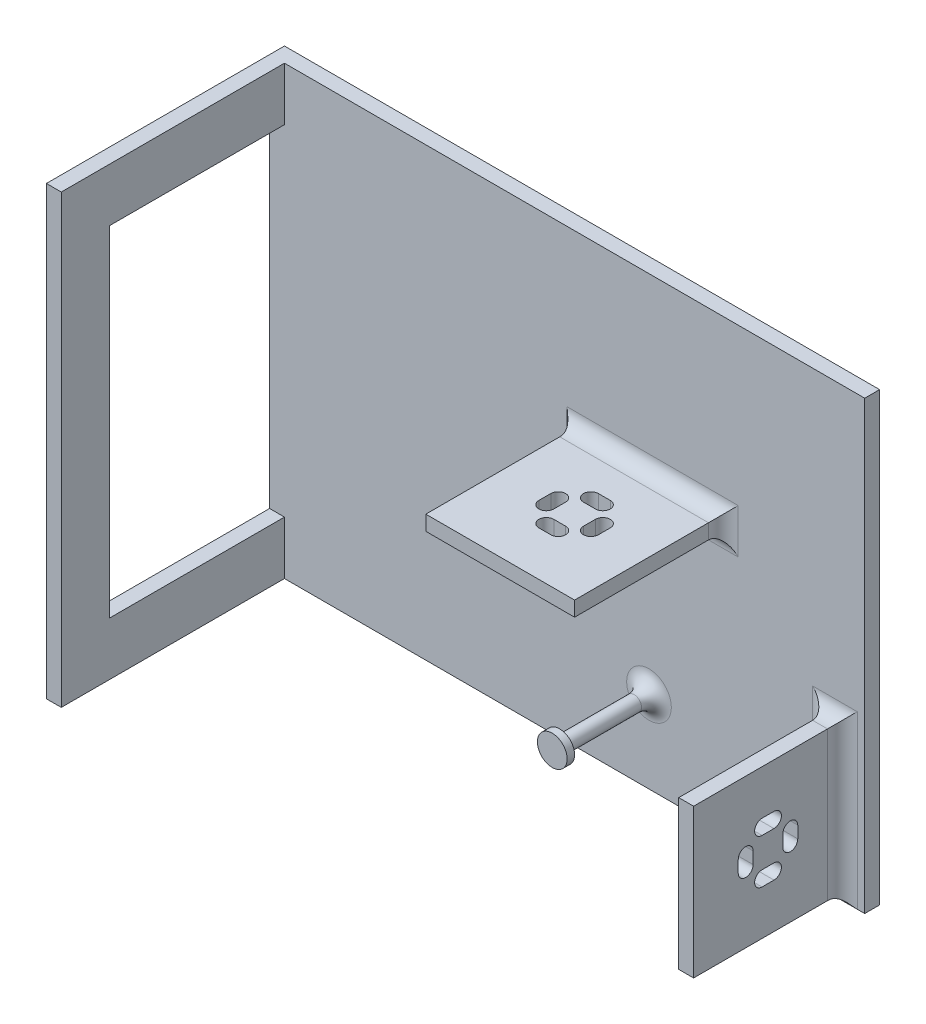
SolidWorks part; units mm, degrees
ref_plane "Front Plane" through (0, 0, 0) normal (0, 0, 1) x (1, 0, 0)
ref_plane "Top Plane" through (0, 0, 0) normal (0, 1, 0) x (1, 0, 0)
ref_plane "Right Plane" through (0, 0, 0) normal (1, 0, 0) x (0, 0, -1)
sketch "Sketch1" plane through (0, 0, 0) normal (0, 0, 1) x (1, 0, 0)
  line L1 (-25.4, -25.4) -> (25.4, -25.4)
  line L2 (-25.4, -25.4) -> (-25.4, 25.4)
  line L3 (-25.4, 25.4) -> (25.4, 25.4)
  line L4 (25.4, -25.4) -> (25.4, 25.4)
  line L5 (-25.4, -25.4) -> (25.4, 25.4) construction
  line L6 (-25.4, 25.4) -> (25.4, -25.4) construction
  point P0 (0, 0)
  dimension "D1" = 50.8
  dimension "D2" = 50.8
extrude "base" add sketch "Sketch1" along normal blind 2.54
sketch "Sketch2" plane through (0, 0, 2.54) normal (0, 0, 1) x (1, 0, 0)
  circle A0 centre (-11.43, -11.43) radius 1.27
  dimension "D1" = 2.54
extrude "post for wing" add sketch "Sketch2" along normal blind 15.24
sketch "Sketch4" plane through (0, 0, 2.54) normal (0, 0, 1) x (1, 0, 0)
  line L1 (-24.13, 19.05) -> (1.27, 19.05)
  line L2 (-24.13, 19.05) -> (-24.13, 21.59)
  line L3 (-24.13, 21.59) -> (1.27, 21.59)
  line L4 (1.27, 19.05) -> (1.27, 21.59)
  line L5 (-24.13, 19.05) -> (1.27, 21.59) construction
  line L6 (-24.13, 21.59) -> (1.27, 19.05) construction
  point P0 (-11.43, 20.32)
  dimension "D1" = 2.54
  dimension "D2" = 25.4
extrude "button holder" add sketch "Sketch4" along normal blind 25.4
ref_point "centre of button"
ref_axis "button axis" through (-11.43, 21.59, 15.24) along (0, 1, 0)
sketch "Sketch6" plane through (0, 21.59, 0) normal (0, 1, 0) x (1, 0, 0)
  line L0 (-12.446, -19.05) -> (-10.414, -19.05) construction
  line L1 (-12.446, -17.78) -> (-10.414, -17.78)
  line L2 (-12.446, -20.32) -> (-10.414, -20.32)
  arc A0 (-12.446, -17.78) -> (-12.446, -20.32) centre (-12.446, -19.05) ccw
  arc A1 (-10.414, -20.32) -> (-10.414, -17.78) centre (-10.414, -19.05) ccw
  point P2 (-11.43, -19.05)
  dimension "D2" = 1.27
  dimension "D1" = 2.032
  dimension "D3" = 0
  dimension "D4" = 3.81
extrude "one button leg hole" cut sketch "Sketch6" against normal blind 6.35
pattern_circular "moar leg holes" count 4 over 360 about axis through (-11.43, 21.59, 15.24) along (0, 1, 0) of "one button leg hole"
fillet "make everything not break" radius 2.54 4 edges at (1.27, 20.32, 2.54) (-11.43, 19.05, 2.54) (-11.43, 21.59, 2.54) (-24.13, 20.32, 2.54)
ref_axis "rotate for second button" through (-11.43, -11.43, 17.78) along (0, 0, -1)
pattern_circular "second button" count 2 every 90 about axis through (-11.43, -11.43, 17.78) along (0, 0, -1) of "button holder", "one button leg hole", "moar leg holes", "make everything not break"
sketch "Sketch3" plane through (0, 0, 17.78) normal (0, 0, 1) x (1, 0, 0)
  circle A0 centre (-11.43, -11.43) radius 2.54
  dimension "D1" = 5.08
extrude "don't let it fall off" add sketch "Sketch3" along normal blind 1.27
fillet "Fillet1" radius 2.54 1 edges at (-12.7, -11.43, 2.54)
sketch "Sketch7" plane through (0, 25.4, 0) normal (0, 1, 0) x (1, 0, 0)
  line L1 (-25.4, 0) -> (25.4, 0)
  line L2 (-25.4, 0) -> (-25.4, -2.54)
  line L3 (-25.4, -2.54) -> (25.4, -2.54)
  line L4 (25.4, 0) -> (25.4, -2.54)
extrude "awkward build 1" add sketch "Sketch7" along normal blind 25.4
sketch "Sketch8" plane through (-25.4, 0, 0) normal (-1, 0, 0) x (0, 0, 1)
  line L1 (0, 50.8) -> (2.54, 50.8)
  line L2 (0, 50.8) -> (0, -25.4)
  line L3 (0, -25.4) -> (2.54, -25.4)
  line L4 (2.54, 50.8) -> (2.54, -25.4)
extrude "awkward build 2" add sketch "Sketch8" along normal blind 50.8
sketch "Sketch9" plane through (0, 0, 2.54) normal (0, 0, 1) x (1, 0, 0)
  line L0 (-76.2, -25.4) -> (16.51, -25.4) construction
  line L1 (-76.2, 50.8) -> (-73.66, 50.8)
  line L2 (-76.2, 50.8) -> (-76.2, -25.4)
  line L3 (-76.2, -25.4) -> (-73.66, -25.4)
  line L4 (-73.66, 50.8) -> (-73.66, -25.4)
  dimension "D1" = 2.54
extrude "camera holder wall" add sketch "Sketch9" along normal blind 38.1
sketch "Sketch10" plane through (-76.2, 0, 0) normal (-1, 0, 0) x (0, 0, 1)
  line L0 (0, 50.8) -> (0, -25.4) construction
  line L1 (2.54, -16.3068) -> (32.4179, -16.3068)
  line L2 (2.54, -16.3068) -> (2.54, 41.7068)
  line L3 (2.54, 41.7068) -> (32.4179, 41.7068)
  line L4 (32.4179, -16.3068) -> (32.4179, 41.7068)
  line L5 (2.54, -16.3068) -> (32.4179, 41.7068) construction
  line L6 (2.54, 41.7068) -> (32.4179, -16.3068) construction
  line L7 (40.64, 50.8) -> (0, 50.8) construction
  point P0 (17.479, 12.7)
  dimension "D1" = 2.54
  dimension "D2" = 58.0136
  dimension "D3" = 38.1
extrude "camera hole" cut sketch "Sketch10" against normal up to next
